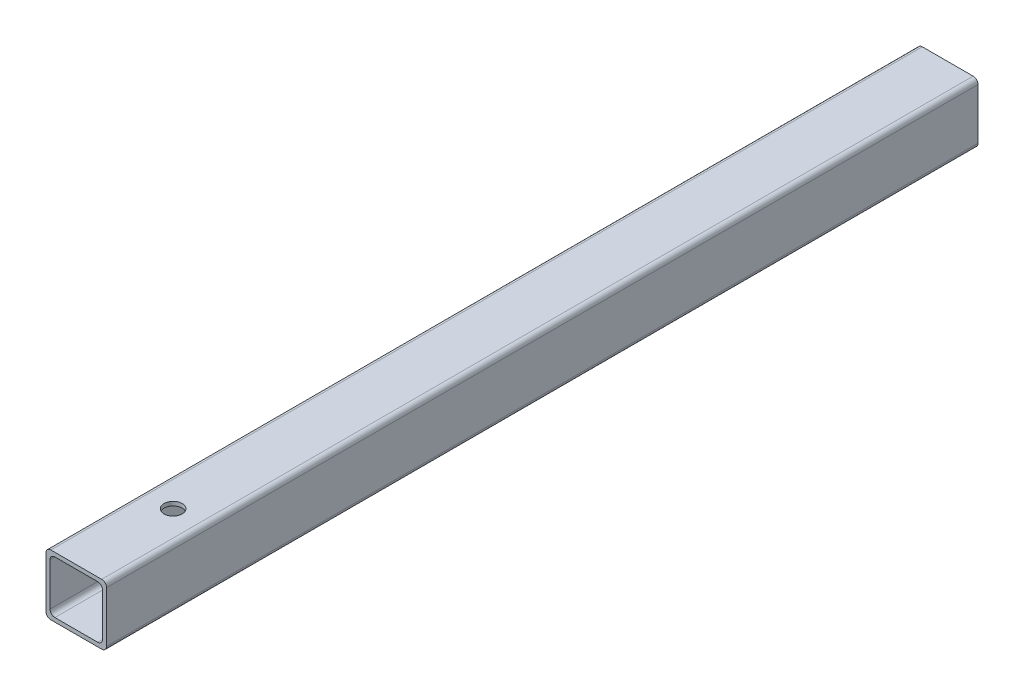
SolidWorks part; units mm, degrees
ref_plane "Front Plane" through (0, 0, 0) normal (0, 0, 1) x (1, 0, 0)
ref_plane "Top Plane" through (0, 0, 0) normal (0, 1, 0) x (1, 0, 0)
ref_plane "Right Plane" through (0, 0, 0) normal (1, 0, 0) x (0, 0, -1)
sketch "Sketch1" plane through (0, 0, 0) normal (0, 0, 1) x (1, 0, 0)
  line L0 (-13.7668, 13.7668) -> (13.7668, 13.7668)
  line L1 (-15.875, -15.875) -> (15.875, -15.875)
  line L2 (-15.875, -15.875) -> (-15.875, 15.875)
  line L3 (-15.875, 15.875) -> (15.875, 15.875)
  line L4 (15.875, -15.875) -> (15.875, 15.875)
  line L5 (-15.875, -15.875) -> (15.875, 15.875) construction
  line L6 (-15.875, 15.875) -> (15.875, -15.875) construction
  line L7 (13.7668, -13.7668) -> (13.7668, 13.7668)
  line L8 (-13.7668, -13.7668) -> (13.7668, -13.7668)
  line L9 (-13.7668, -13.7668) -> (-13.7668, 13.7668)
  point P0 (0, 0)
  dimension "D1" = 31.75
  dimension "D2" = 31.75
  dimension "D3" = 2.1082
extrude "Boss-Extrude1" add sketch "Sketch1" along normal blind 457.2
fillet "Fillet1" radius 2.54 8 edges at (15.875, -15.875, 228.6) (13.7668, -13.7668, 228.6) (13.7668, 13.7668, 228.6) (15.875, 15.875, 228.6) (-13.7668, 13.7668, 228.6) (-15.875, 15.875, 228.6) (-13.7668, -13.7668, 228.6) (-15.875, -15.875, 228.6)
ref_axis "Axis1" through (0, 0, -22.86) along (0, 0, 1)
sketch "Sketch2" plane through (0, 15.875, 0) normal (0, 1, 0) x (1, 0, 0)
  line L0 (0, 22.86) -> (0, -480.06) construction
  line L1 (13.335, -457.2) -> (-13.335, -457.2) construction
  circle A0 centre (0, -406.4) radius 4.7625
  dimension "D2" = 9.525
  dimension "D1" = 50.8
extrude "Cut-Extrude1" cut sketch "Sketch2" against normal through all
